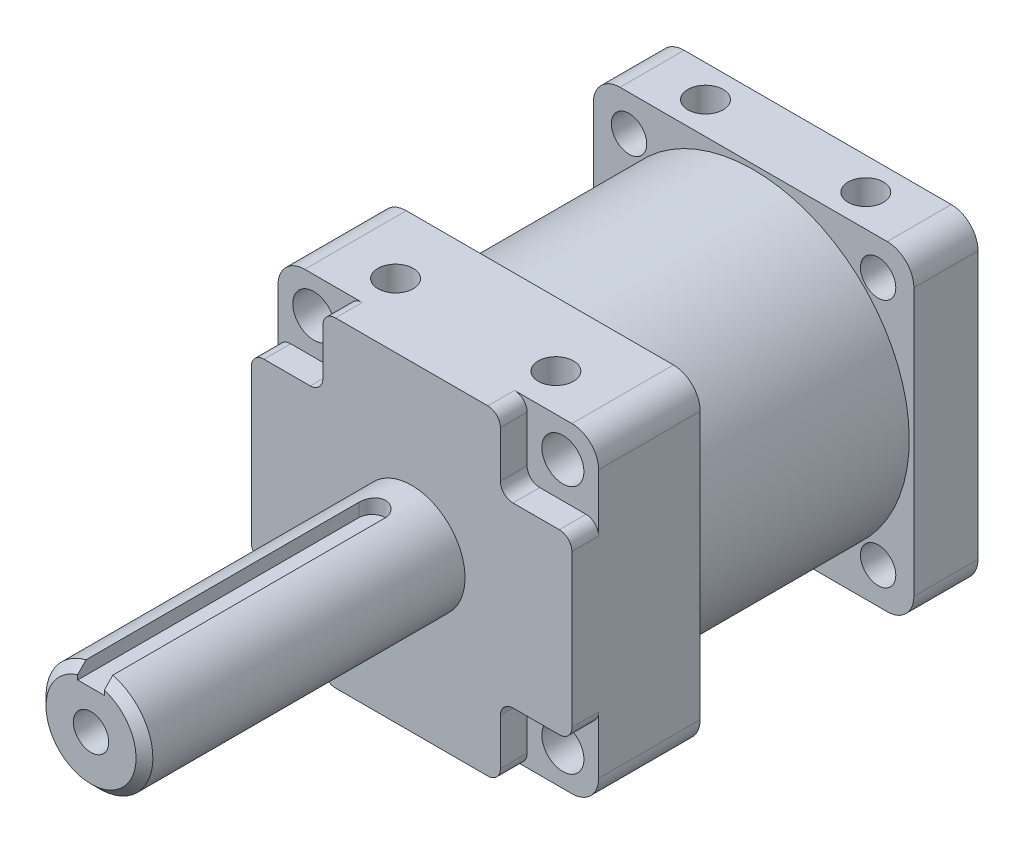
SolidWorks part; units mm, degrees
material "AISI 1045 Steel, cold drawn"
ref_plane "Front Plane" through (0, 0, 0) normal (0, 0, 1) x (1, 0, 0)
ref_plane "Top Plane" through (0, 0, 0) normal (0, 1, 0) x (1, 0, 0)
ref_plane "Right Plane" through (0, 0, 0) normal (1, 0, 0) x (0, 0, -1)
sketch "Sketch1" plane through (0, 0, 0) normal (0, 0, 1) x (1, 0, 0)
  line L1 (-19.05, -19.05) -> (19.05, -19.05)
  line L2 (-19.05, -19.05) -> (-19.05, 19.05)
  line L3 (-19.05, 19.05) -> (19.05, 19.05)
  line L4 (19.05, -19.05) -> (19.05, 19.05)
  line L5 (-19.05, -19.05) -> (19.05, 19.05) construction
  line L6 (-19.05, 19.05) -> (19.05, -19.05) construction
  point P0 (0, 0)
  dimension "D1" = 38.1
extrude "Extrude1" add sketch "Sketch1" along normal blind 15.24
fillet "Fillet1" radius 3.175 4 edges at (-19.05, -19.05, 7.62) (19.05, -19.05, 7.62) (19.05, 19.05, 7.62) (-19.05, 19.05, 7.62)
sketch "Sketch2" plane through (0, 0, 15.24) normal (0, 0, 1) x (1, 0, 0)
  circle A0 centre (0, 0) radius 6.35
  dimension "D1" = 12.7
extrude "Extrude2" add sketch "Sketch2" along normal blind 38.1
chamfer "Chamfer1" distance 1 angle 45 1 edges at (6.35, 0, 53.34)
sketch "Sketch3" plane through (0, 0, 53.34) normal (0, 0, 1) x (1, 0, 0)
  line L0 (-1.5875, 6.1484) -> (0, 6.1484) construction
  line L1 (-1.5875, 4.5609) -> (1.5875, 4.5609)
  line L2 (-1.5875, 4.5609) -> (-1.5875, 7.7359)
  line L3 (-1.5875, 7.7359) -> (1.5875, 7.7359)
  line L4 (1.5875, 4.5609) -> (1.5875, 7.7359)
  line L5 (-1.5875, 4.5609) -> (1.5875, 7.7359) construction
  line L6 (-1.5875, 7.7359) -> (1.5875, 4.5609) construction
  line L7 (0, 0) -> (0, 6.1484) construction
  circle A0 centre (0, 0) radius 6.35 construction
  point P0 (0, 6.1484)
  dimension "D1" = 3.175
extrude "Extrude3" cut sketch "Sketch3" against normal blind 35
fillet "Fillet2" 2 edges at (-1.5875, 5.3546, 18.34) (1.5875, 5.3546, 18.34) type full round first side face at (-1.5875, 5.4094, 39.04) second side face at (1.5875, 5.2016, 39.24) middle face at (0, 5.405, 18.34)
hole_wizard "M5x0.8 Tapped Hole1" positions "Sketch6" profile "Sketch5" tap size "M5x0.8" standard "Ansi Metric"
sketch "Sketch6" plane through (0, 0, 53.34) normal (0, 0, 1) x (1, 0, 0)
  point P0 (0, 0)
sketch "Sketch5" plane through (0, 0, 53.34) normal (1, 0, 0) x (0, -1, 0)
  line L0 (0, 0) -> (0, 15.2618)
  line L1 (0, 15.2618) -> (2.1, 14)
  line L2 (2.1, 14) -> (2.1, 0)
  line L5 (2.1, 0) -> (0, 0)
  line L10 (0, 15.2618) -> (-2.1, 14) construction
  line L11 (0, -6.35) -> (0, 107.95) construction
  dimension "Tap Drill Dia." = 4.2
  dimension "Tap Drill Depth" = 14
  dimension "Drill Angle" = 118
cosmetic thread "Hole Thread1" parameters "D1"=10, "D2"=5
sketch "Sketch7" plane through (0, 0, 0) normal (0, 0, -1) x (-1, 0, 0)
  circle A0 centre (0, 0) radius 18.5
  dimension "D1" = 37
extrude "Extrude4" add sketch "Sketch7" along normal blind 25.4
sketch "Sketch8" plane through (0, 0, -25.4) normal (0, 0, -1) x (-1, 0, 0)
  line L8 (-15.875, -19.05) -> (15.875, -19.05)
  line L9 (19.05, -15.875) -> (19.05, 15.875)
  line L10 (15.875, 19.05) -> (-15.875, 19.05)
  line L11 (-19.05, 15.875) -> (-19.05, -15.875)
  line L12 (-15.875, -19.05) -> (15.875, -19.05)
  line L13 (19.05, -15.875) -> (19.05, 15.875)
  line L14 (15.875, 19.05) -> (-15.875, 19.05)
  line L15 (-19.05, 15.875) -> (-19.05, -15.875)
  arc A9 (15.875, -19.05) -> (19.05, -15.875) centre (15.875, -15.875) ccw
  arc A10 (19.05, 15.875) -> (15.875, 19.05) centre (15.875, 15.875) ccw
  arc A11 (-15.875, 19.05) -> (-19.05, 15.875) centre (-15.875, 15.875) ccw
  arc A12 (-19.05, -15.875) -> (-15.875, -19.05) centre (-15.875, -15.875) ccw
  arc A13 (15.875, -19.05) -> (19.05, -15.875) centre (15.875, -15.875) ccw
  arc A14 (19.05, 15.875) -> (15.875, 19.05) centre (15.875, 15.875) ccw
  arc A15 (-15.875, 19.05) -> (-19.05, 15.875) centre (-15.875, 15.875) ccw
  arc A16 (-19.05, -15.875) -> (-15.875, -19.05) centre (-15.875, -15.875) ccw
  dimension "D1" = 0
extrude "Extrude5" add sketch "Sketch8" along normal blind 7.62
sketch "Sketch9" plane through (0, 0, 15.24) normal (0, 0, 1) x (1, 0, 0)
  line L0 (15.875, 19.05) -> (-15.875, 19.05) construction
  line L1 (-19.05, 19.05) -> (-10.55, 19.05)
  line L2 (-19.05, 19.05) -> (-19.05, 10.55)
  line L3 (-19.05, 10.55) -> (-10.55, 10.55)
  line L4 (-10.55, 19.05) -> (-10.55, 10.55)
  line L5 (-19.05, 15.875) -> (-19.05, -15.875) construction
  line L6 (0, 0) -> (-19.05, 0) construction
  line L7 (0, 0) -> (0, 19.05) construction
  line L8 (10.55, 19.05) -> (10.55, 10.55)
  line L9 (19.05, 10.55) -> (10.55, 10.55)
  line L10 (19.05, 19.05) -> (19.05, 10.55)
  line L11 (19.05, 19.05) -> (10.55, 19.05)
  line L12 (19.05, -19.05) -> (10.55, -19.05)
  line L13 (19.05, -19.05) -> (19.05, -10.55)
  line L14 (19.05, -10.55) -> (10.55, -10.55)
  line L15 (10.55, -19.05) -> (10.55, -10.55)
  line L16 (-10.55, -19.05) -> (-10.55, -10.55)
  line L17 (-19.05, -10.55) -> (-10.55, -10.55)
  line L18 (-19.05, -19.05) -> (-19.05, -10.55)
  line L19 (-19.05, -19.05) -> (-10.55, -19.05)
  dimension "D1" = 8.5
extrude "Extrude7" cut sketch "Sketch9" against normal blind 3.175
fillet "Fillet3" radius 1.5 12 edges at (-19.05, 10.55, 13.6525) (-10.55, 19.05, 13.6525) (-10.55, 10.55, 13.6525) (10.55, -19.05, 13.6525) (10.55, -10.55, 13.6525) (19.05, -10.55, 13.6525) (19.05, 10.55, 13.6525) (10.55, 10.55, 13.6525) (10.55, 19.05, 13.6525) (-10.55, -19.05, 13.6525) (-10.55, -10.55, 13.6525) (-19.05, -10.55, 13.6525)
sketch "Sketch10" plane through (0, 0, 12.065) normal (0, 0, 1) x (1, 0, 0)
  line L0 (-19.05, 14.8) -> (-14.8, 14.8) construction
  line L1 (-19.05, 15.875) -> (-19.05, 9.05) construction
  line L2 (-14.8, 14.8) -> (-10.55, 14.8) construction
  line L3 (-10.55, 12.05) -> (-10.55, 17.55) construction
  line L4 (-14.8, 19.05) -> (-14.8, 14.8) construction
  line L5 (-9.05, 19.05) -> (-15.875, 19.05) construction
  line L6 (-14.8, 14.8) -> (-14.8, 10.55) construction
  line L7 (-17.55, 10.55) -> (-12.05, 10.55) construction
  line L8 (0, 0) -> (-13.8093, 0) construction
  line L9 (0, 0) -> (0, 8.8405) construction
  circle A0 centre (-14.8, 14.8) radius 2.5
  circle A1 centre (-14.8, -14.8) radius 2.5
  circle A2 centre (14.8, -14.8) radius 2.5
  circle A3 centre (14.8, 14.8) radius 2.5
  dimension "D1" = 5
extrude "Extrude8" cut sketch "Sketch10" against normal up to surface (12.065 mm away) up to face at (0, 0, 0)
hole_wizard "M5x0.8 Tapped Hole2" positions "Sketch12" profile "Sketch11" tap size "M5x0.8" standard "Ansi Metric" end condition through all
sketch "Sketch12" plane through (0, 0, -25.4) normal (0, 0, 1) x (1, 0, 0)
  point P0 (-14.8, 14.8)
  point P1 (14.8, 14.8)
  point P4 (14.8, -14.8)
  point P7 (-14.8, -14.8)
sketch "Sketch11" plane through (-14.8, 14.8, -25.4) normal (1, 0, 0) x (0, -1, 0)
  line L0 (0, 0) -> (0, 7.62)
  line L1 (0, 7.62) -> (2.1, 7.62)
  line L2 (2.1, 7.62) -> (2.1, 0)
  line L5 (2.1, 0) -> (0, 0)
  line L11 (0, -6.35) -> (0, 107.95) construction
  dimension "Thru Tap Drill Dia." = 4.2
  dimension "Thru Tap Drill Depth" = 7.62
cosmetic thread "Hole Thread2" parameters "D2"=5
cosmetic thread "Hole Thread3" parameters "D2"=5
cosmetic thread "Hole Thread4" parameters "D2"=5
cosmetic thread "Hole Thread5" parameters "D2"=5
hole_wizard "M5x0.8 Tapped Hole3" positions "Sketch14" profile "Sketch13" tap size "M5x0.8" standard "Ansi Metric"
sketch "Sketch14" plane through (0, 19.05, 0) normal (0, 1, 0) x (-1, 0, 0)
  line L0 (0, -33.02) -> (0, -29.21) construction
  line L1 (15.875, -33.02) -> (-15.875, -33.02) construction
  line L2 (0, -29.21) -> (0, -25.4) construction
  line L3 (15.875, -25.4) -> (-15.875, -25.4) construction
  line L5 (0, -29.21) -> (9.525, -29.21) construction
  line L6 (0, -29.21) -> (-9.525, -29.21) construction
  line L7 (0, 0) -> (0, 7.62) construction
  line L8 (0, 7.62) -> (9.525, 7.62) construction
  line L10 (0, 7.62) -> (-9.525, 7.62) construction
  line L11 (-9.05, 15.24) -> (9.05, 15.24) construction
  point P0 (9.525, -29.21)
  point P23 (-9.525, -29.21)
  point P41 (9.525, 7.62)
  point P43 (-9.525, 7.62)
  dimension "D1" = 9.525
  dimension "D2" = 7.62
sketch "Sketch13" plane through (-9.525, 19.05, -29.21) normal (1, 0, 0) x (0, 0, 1)
  line L0 (0, 0) -> (0, 8.8818)
  line L1 (0, 8.8818) -> (2.1, 7.62)
  line L2 (2.1, 7.62) -> (2.1, 0)
  line L5 (2.1, 0) -> (0, 0)
  line L10 (0, 8.8818) -> (-2.1, 7.62) construction
  line L11 (0, -6.35) -> (0, 107.95) construction
  dimension "Tap Drill Dia." = 4.2
  dimension "Tap Drill Depth" = 7.62
  dimension "Drill Angle" = 118
cosmetic thread "Hole Thread6" parameters "D1"=7.62, "D2"=5
cosmetic thread "Hole Thread7" parameters "D1"=7.62, "D2"=5
cosmetic thread "Hole Thread8" parameters "D1"=7.62, "D2"=5
cosmetic thread "Hole Thread9" parameters "D1"=7.62, "D2"=5
mirror "Mirror2" about plane through (0, 0, 0) normal (0, 1, 0) of "M5x0.8 Tapped Hole3"
